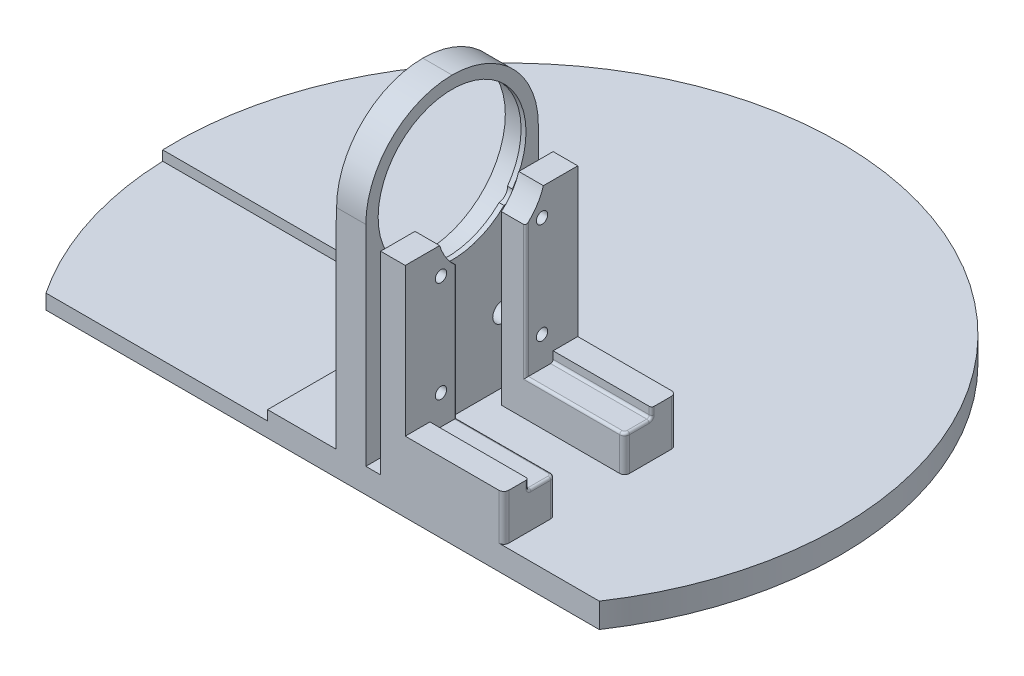
SolidWorks part; units mm, degrees
ref_plane "정면" through (0, 0, 0) normal (0, 0, 1) x (1, 0, 0)
ref_plane "윗면" through (0, 0, 0) normal (0, 1, 0) x (1, 0, 0)
ref_plane "우측면" through (0, 0, 0) normal (1, 0, 0) x (0, 0, -1)
sketch "스케치1" plane through (0, 0, 0) normal (0, 1, 0) x (1, 0, 0)
  circle A0 centre (0, 0) radius 67.5
  dimension "D1" = 135
extrude "보스-돌출1" add sketch "스케치1" along normal blind 5
sketch "스케치2" plane through (0, 5, 0) normal (0, 1, 0) x (1, 0, 0)
  line L1 (2.76, -2.5) -> (8.76, -2.5)
  line L2 (2.76, -2.5) -> (2.76, -37.5)
  line L3 (2.76, -37.5) -> (8.76, -37.5)
  line L4 (8.76, -2.5) -> (8.76, -37.5)
  point P4 (8.76, -20)
  dimension "D1" = 2.76
  dimension "D2" = 6
  dimension "D3" = 35
  dimension "D4" = 20
extrude "보스-돌출2" add sketch "스케치2" along normal blind 60
fillet "필렛1" radius 17.5 2 edges at (5.76, 65, 2.5) (5.76, 65, 37.5)
sketch "스케치3" plane through (2.76, 0, 0) normal (-1, 0, 0) x (0, 0, 1)
  circle A0 centre (20, 47.5) radius 16
  dimension "D1" = 32
extrude "컷-돌출1" cut sketch "스케치3" against normal blind 5
chamfer "모따기1" distance 0.8 angle 64 1 edges at (2.76, 47.5, 36) first distance on face at (7.76, 47.5, 36)
sketch "스케치4" plane through (7.76, 0, 0) normal (-1, 0, 0) x (0, 0, 1)
  circle A0 centre (20, 47.5) radius 15
  circle A1 centre (20, 47.5) radius 16 construction
  dimension "D1" = 1
extrude "컷-돌출2" cut sketch "스케치4" against normal through all
sketch "스케치6" plane through (8.76, 0, 0) normal (1, 0, 0) x (0, 0, -1)
  line L5 (-2.5, 27.5) -> (-2.5, 21.5)
  line L6 (-2.5, 27.5) -> (-4.5, 27.5)
  line L7 (-2.5, 21.5) -> (-4.5, 21.5)
  line L8 (-4.5, 27.5) -> (-4.5, 21.5)
  line L9 (-2.5, 47.5) -> (-2.5, 5) construction
  circle A0 centre (-20, 47.5) radius 15 construction
  dimension "D4" = 20
  dimension "D2" = 2
extrude "컷-돌출3" cut sketch "스케치6" against normal through all
sketch "스케치8" plane through (0, 0, 4.5) normal (0, 0, -1) x (-1, 0, 0)
  line L0 (-2.76, 27.5) -> (-8.76, 27.5) construction
  line L1 (-2.76, 27.5) -> (-2.76, 21.5) construction
  circle A0 centre (-5.76, 24.5) radius 1.6
  dimension "D1" = 3
  dimension "D2" = 3
  dimension "D3" = 3.2
extrude "컷-돌출5" cut sketch "스케치8" against normal blind 6
sketch "스케치9" plane through (0, 0, 4.5) normal (0, 0, -1) x (-1, 0, 0)
  line L0 (-2.76, 21.5) -> (-8.76, 21.5) construction
  line L3 (-4.3166, 27) -> (-7.2034, 27)
  line L4 (-7.2034, 27) -> (-8.6468, 24.5)
  line L5 (-8.6468, 24.5) -> (-7.2034, 22)
  line L6 (-7.2034, 22) -> (-4.3166, 22)
  line L7 (-4.3166, 27) -> (-2.76, 27)
  line L8 (-2.76, 27.5) -> (-2.76, 21.5) construction
  line L9 (-2.76, 27) -> (-2.76, 22)
  line L10 (-2.76, 22) -> (-4.3166, 22)
  line L12 (-2.8732, 24.5) -> (-4.3166, 27) [skipped]
  line L13 (-4.3166, 22) -> (-2.8732, 24.5) [skipped]
  circle A0 centre (-5.76, 24.5) radius 2.5 construction
  dimension "D1" = 5
extrude "컷-돌출8" cut sketch "스케치9" against normal blind 2.2 from offset 2 offset against normal yes
sketch "스케치11" plane through (0, 5, 0) normal (0, 1, 0) x (1, 0, 0)
  line L0 (11.76, -2.5) -> (36.76, -2.5)
  line L1 (11.76, -2.5) -> (11.76, -13)
  line L2 (36.76, -2.5) -> (36.76, -13)
  line L3 (11.76, -13) -> (36.76, -13)
  line L4 (11.76, -27) -> (36.76, -27)
  line L5 (11.76, -27) -> (11.76, -37.5)
  line L6 (36.76, -27) -> (36.76, -37.5)
  line L7 (11.76, -37.5) -> (36.76, -37.5)
  line L8 (8.76, -2.5) -> (2.76, -2.5) construction
  line L9 (8.76, -37.5) -> (8.76, -2.5) construction
  dimension "D1" = 35
  dimension "D2" = 10.5
  dimension "D3" = 3
  dimension "D4" = 25
extrude "보스-돌출4" add sketch "스케치11" along normal blind 7.3
sketch "스케치12" plane through (0, 12.3, 0) normal (0, 1, 0) x (1, 0, 0)
  line L0 (16.76, -32.5) -> (36.76, -32.5)
  line L1 (11.76, -2.5) -> (36.76, -2.5)
  line L2 (11.76, -2.5) -> (11.76, -13)
  line L3 (11.76, -13) -> (16.76, -13)
  line L4 (36.76, -2.5) -> (36.76, -7.5)
  line L5 (11.76, -27) -> (16.76, -27)
  line L6 (11.76, -27) -> (11.76, -37.5)
  line L7 (11.76, -37.5) -> (36.76, -37.5)
  line L8 (36.76, -32.5) -> (36.76, -37.5)
  line L9 (16.76, -7.5) -> (36.76, -7.5)
  line L10 (16.76, -7.5) -> (16.76, -13)
  line L11 (16.76, -27) -> (16.76, -32.5)
  line L12 (11.76, -13) -> (36.76, -13) construction
  line L13 (11.76, -27) -> (36.76, -27) construction
  line L14 (16.76, -2.5) -> (16.76, -13) construction
  line L15 (11.76, -7.5) -> (36.76, -7.5) construction
  line L16 (11.76, -32.5) -> (36.76, -32.5) construction
  line L17 (16.76, -27) -> (16.76, -37.5) construction
  dimension "D1" = 5.5
  dimension "D2" = 5.5
  dimension "D3" = 5
extrude "보스-돌출5" add sketch "스케치12" along normal blind 2
fillet "필렛3" radius 1 4 edges at (36.76, 8.65, 27) (36.76, 8.65, 13) (36.76, 9.65, 2.5) (36.76, 9.65, 37.5)
sketch "스케치13" plane through (16.76, 0, 0) normal (1, 0, 0) x (0, 0, -1)
  line L0 (-27, 14.3) -> (-37.5, 14.3)
  line L1 (-27, 14.3) -> (-27, 39.0147)
  line L2 (-37.5, 14.3) -> (-37.5, 44.3)
  line L3 (-30.5243, 44.3) -> (-37.5, 44.3)
  line L4 (-13, 14.3) -> (-2.5, 14.3)
  line L5 (-13, 14.3) -> (-13, 39.0147)
  line L6 (-2.5, 14.3) -> (-2.5, 44.3)
  line L7 (-9.4757, 44.3) -> (-2.5, 44.3)
  line L10 (-2.5, 21.5) -> (-2.5, 5) construction
  arc A0 (-30.5243, 44.3) -> (-27, 39.0147) centre (-20, 47.5) ccw
  arc A1 (-13, 39.0147) -> (-9.4757, 44.3) centre (-20, 47.5) ccw
  dimension "D2" = 22
  dimension "D1" = 30
extrude "보스-돌출6" add sketch "스케치13" against normal blind 5
sketch "스케치14" plane through (16.76, 0, 0) normal (1, 0, 0) x (0, 0, -1)
  line L1 (-30.25, 38.8) -> (-9.75, 38.8) construction
  line L2 (-30.25, 38.8) -> (-30.25, 18.3) construction
  line L3 (-30.25, 18.3) -> (-9.75, 18.3) construction
  line L4 (-9.75, 38.8) -> (-9.75, 18.3) construction
  line L8 (-32.5, 12.3) -> (-27, 12.3) construction
  circle A1 centre (-20, 47.5) radius 15 construction
  circle A2 centre (-30.25, 18.3) radius 1.15
  circle A3 centre (-9.75, 18.3) radius 1.15
  circle A4 centre (-9.75, 38.8) radius 1.15
  circle A5 centre (-30.25, 38.8) radius 1.15
  dimension "D5" = 2.3
  dimension "D1" = 20.5
  dimension "D2" = 20.5
  dimension "D3" = 6
  dimension "D4" = 10.25
extrude "컷-돌출10" cut sketch "스케치14" against normal through all
fillet "필렛2" radius 0.5 12 edges at (26.76, 12.3, 32.5) (26.76, 12.3, 7.5) (36.76, 13.3, 7.5) (36.76, 13.3, 32.5) (36.76, 12.3, 9.75) (36.76, 12.3, 30.25) (26.26, 12.3, 13) (36.4671, 12.3, 12.7071) (26.26, 12.3, 27) (36.4671, 12.3, 27.2929) (16.76, 25.6574, 13) (16.76, 25.6574, 27)
sketch "스케치15" plane through (2.76, 0, 0) normal (-1, 0, 0) x (0, 0, 1)
  circle A0 centre (9.75, 38.8) radius 2
  circle A1 centre (30.25, 38.8) radius 2
  circle A2 centre (9.75, 18.3) radius 2
  circle A3 centre (30.25, 18.3) radius 2
  dimension "D1" = 4
extrude "컷-돌출11" cut sketch "스케치15" against normal blind 10
sketch "스케치16" plane through (0, 5, 0) normal (0, 1, 0) x (1, 0, 0)
  line L0 (2.8284, -2.5) -> (2.8284, -20) construction
  line L1 (-11.1716, -2.5) -> (-67.5, -2.5)
  line L2 (-11.1716, -2.5) -> (-11.1716, -67.5)
  line L3 (-11.1716, -67.5) -> (-67.5, -67.5)
  line L4 (-67.5, -2.5) -> (-67.5, -67.5)
  line L6 (35.76, -2.5) -> (16.76, -2.5) construction
  circle A0 centre (0, 0) radius 67.5 construction
  dimension "D2" = 14
extrude "컷-돌출12" cut sketch "스케치16" against normal blind 2
sketch "스케치17" plane through (0, 5, 0) normal (0, 1, 0) x (1, 0, 0)
  line L0 (11.76, -37.5) -> (35.76, -37.5) construction
  line L1 (56.1249, -37.5) -> (-56.1249, -37.5)
  line L2 (56.1249, -37.5) -> (56.1249, -67.5)
  line L3 (56.1249, -67.5) -> (-56.1249, -67.5)
  line L4 (-56.1249, -37.5) -> (-56.1249, -67.5)
  arc A0 (-11.1716, -66.5691) -> (-67.4537, -2.5) centre (0, 0) ccw construction
  point P4 (0, 0)
  point P6 (0, 0)
  point P12 (0, 0)
extrude "컷-돌출13" cut sketch "스케치17" against normal through all
